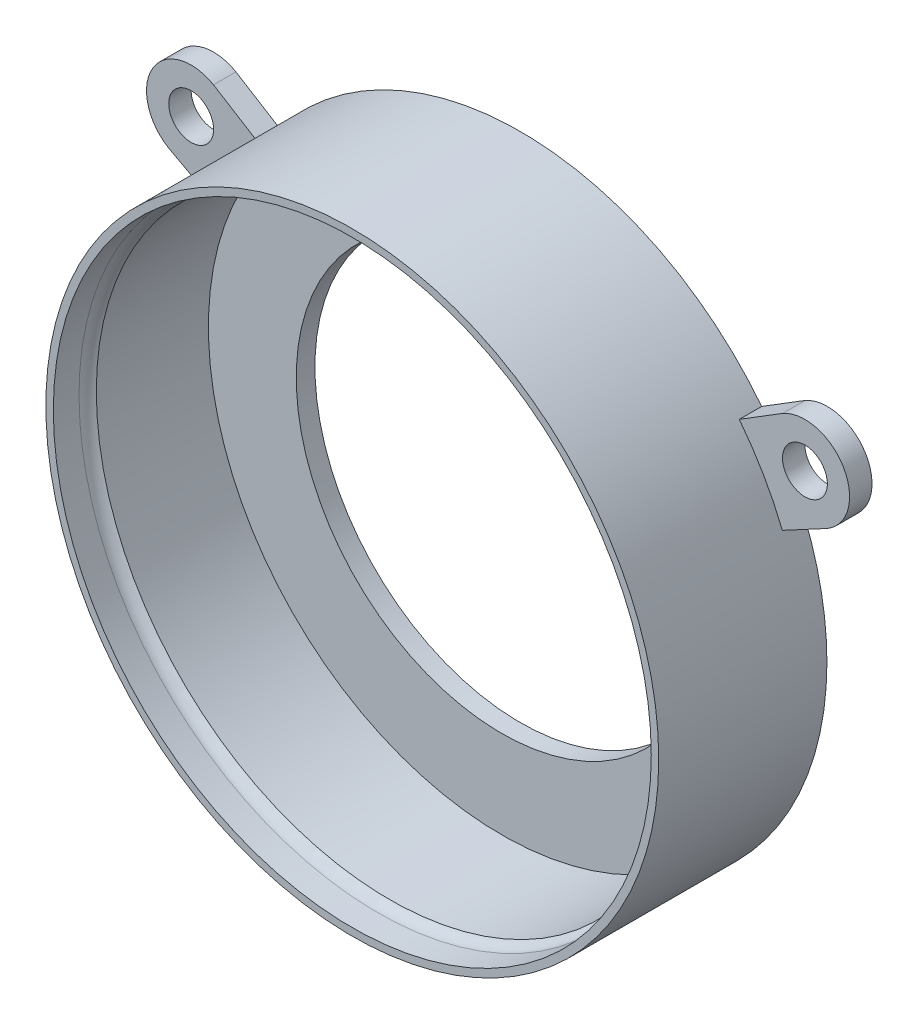
SolidWorks part; units mm, degrees
ref_plane "Front Plane" through (0, 0, 0) normal (1, 0, 0) x (0, 1, 0)
ref_plane "Top Plane" through (0, 0, 0) normal (0, 0, 1) x (0, 1, 0)
ref_plane "Right Plane" through (0, 0, 0) normal (0, 1, 0) x (-1, 0, 0)
sketch "Sketch1" plane through (0, 0, 0) normal (0, 0, 1) x (0, 1, 0)
  circle A0 centre (0, 0) radius 27.5
  circle A1 centre (0, 0) radius 41
  circle A2 centre (0, 0) radius 39.25
  dimension "D1" = 55
  dimension "D2" = 82
  dimension "D3" = 78.5
extrude "Boss-Extrude1" add sketch "Sketch1" against normal blind 2.5 contours A2 A0 | A1 A2 region at (0, -39.8403, 0) region at (0, -38.1398, 0)
extrude "Boss-Extrude2" add sketch "Sketch1<3>" along normal blind 15 contours A1 A2 region at (0, -39.8403, 0)
sketch "Sketch1<3>" plane through (0, 0, 0) normal (0, 0, 1) x (0, 1, 0) same geometry as "Sketch1"
sketch "Sketch2" plane through (0, 0, -2.5) normal (0, 0, -1) x (1, 0, 0)
  line L0 (5.9728, 47.4089) -> (5.762, 40.5931)
  line L3 (-5.9728, 47.4089) -> (-5.762, 40.5931)
  line L10 (38.0709, -28.877) -> (32.2737, -25.2866)
  line L11 (44.0437, -18.5319) -> (38.0356, -15.3065)
  line L12 (-44.0437, -18.5319) -> (-38.0356, -15.3065)
  line L13 (-38.0709, -28.877) -> (-32.2737, -25.2866)
  arc A5 (5.9728, 47.4089) -> (-5.9728, 47.4089) centre (0, 47.4089) ccw
  arc A6 (5.762, 40.5931) -> (-5.762, 40.5931) centre (0, 0) ccw
  circle A7 centre (0, 47.4089) radius 3
  arc A17 (38.0709, -28.877) -> (44.0437, -18.5319) centre (41.0573, -23.7044) ccw
  arc A18 (32.2737, -25.2866) -> (38.0356, -15.3065) centre (0, 0) ccw
  circle A19 centre (41.0573, -23.7044) radius 3
  arc A20 (-44.0437, -18.5319) -> (-38.0709, -28.877) centre (-41.0573, -23.7044) ccw
  arc A21 (-38.0356, -15.3065) -> (-32.2737, -25.2866) centre (0, 0) ccw
  circle A22 centre (-41.0573, -23.7044) radius 3
  point P0 (0, -41.3739)
  point P2 (41.3739, 0)
  point P6 (35.8308, -20.6869)
  point P15 (0, 41.3739)
  point P21 (-35.8308, -20.6869)
  point P26 (0, 0)
  dimension "D1" = 3
extrude "Boss-Extrude3" add sketch "Sketch2" against normal blind 3
sketch "Sketch3" plane through (0, 0, 15) normal (0, 0, 1) x (1, 0, 0)
  circle A0 centre (0, 0) radius 41 construction
  circle A1 centre (0, 0) radius 41
  circle A2 centre (0, 0) radius 40
  dimension "D1" = 1
extrude "Boss-Extrude4" add sketch "Sketch3" along normal blind 5
fillet "Fillet4" radius 2 1 edges at (40, 0, 15)
